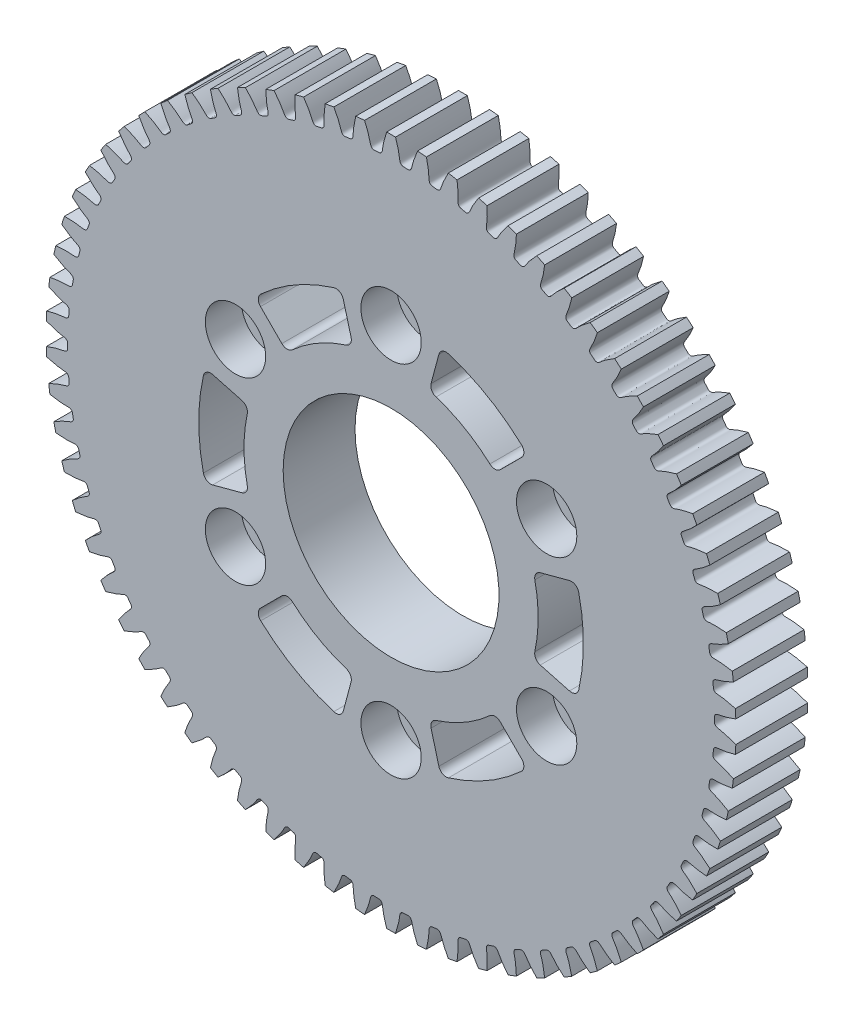
SolidWorks part; units mm, degrees
material "7075-T6 (SN)"
ref_plane "Front Plane" through (0, 0, 0) normal (0, 0, 1) x (1, 0, 0)
ref_plane "Top Plane" through (0, 0, 0) normal (0, 1, 0) x (1, 0, 0)
ref_plane "Right Plane" through (0, 0, 0) normal (1, 0, 0) x (0, 0, -1)
ref_axis "Axis4" through (0, 0, 0) along (0, 0, 1)
sketch "Sketch1" plane through (0, 0, 0) normal (0, 0, 1) x (1, 0, 0)
  arc A0 (45.2238, -6.7177) -> (45.3812, -5.5556) centre (0, 0) ccw
  arc A1 (45.6439, -2.6368) -> (45.6965, -1.4653) centre (0, 0) ccw
  arc A2 (45.6965, 1.4653) -> (45.6439, 2.6368) centre (0, 0) ccw
  arc A3 (45.3812, 5.5556) -> (45.2238, 6.7177) centre (0, 0) ccw
  arc A4 (44.7005, 9.6011) -> (44.4396, 10.7445) centre (0, 0) ccw
  arc A5 (43.6599, 13.5694) -> (43.2975, 14.6848) centre (0, 0) ccw
  arc A6 (42.2678, 17.4284) -> (41.8069, 18.5068) centre (0, 0) ccw
  arc A7 (40.5354, 21.1471) -> (39.9797, 22.1799) centre (0, 0) ccw
  arc A8 (38.4766, 24.6956) -> (37.8305, 25.6743) centre (0, 0) ccw
  arc A9 (36.108, 28.0452) -> (35.3768, 28.9621) centre (0, 0) ccw
  arc A10 (33.4487, 31.169) -> (32.6382, 32.0166) centre (0, 0) ccw
  arc A11 (30.5201, 34.0418) -> (29.6369, 34.8134) centre (0, 0) ccw
  arc A12 (27.3457, 36.6406) -> (26.3969, 37.3299) centre (0, 0) ccw
  arc A13 (23.9512, 38.9443) -> (22.9445, 39.5458) centre (0, 0) ccw
  arc A14 (20.3638, 40.9345) -> (19.3072, 41.4433) centre (0, 0) ccw
  arc A15 (16.6125, 42.5951) -> (15.5145, 43.0072) centre (0, 0) ccw
  arc A16 (12.7274, 43.9128) -> (11.597, 44.2248) centre (0, 0) ccw
  arc A17 (8.7399, 44.8769) -> (7.586, 45.0863) centre (0, 0) ccw
  arc A18 (4.682, 45.4796) -> (3.514, 45.5848) centre (0, 0) ccw
  arc A19 (0.5864, 45.7162) -> (-0.5864, 45.7162) centre (0, 0) ccw
  arc A20 (-3.514, 45.5848) -> (-4.682, 45.4796) centre (0, 0) ccw
  arc A21 (-7.586, 45.0863) -> (-8.7399, 44.8769) centre (0, 0) ccw
  arc A22 (-11.597, 44.2248) -> (-12.7274, 43.9128) centre (0, 0) ccw
  arc A23 (-15.5145, 43.0072) -> (-16.6125, 42.5951) centre (0, 0) ccw
  arc A24 (-19.3072, 41.4433) -> (-20.3638, 40.9345) centre (0, 0) ccw
  arc A25 (-22.9445, 39.5458) -> (-23.9512, 38.9443) centre (0, 0) ccw
  arc A26 (-26.3969, 37.3299) -> (-27.3457, 36.6406) centre (0, 0) ccw
  arc A27 (-29.6369, 34.8134) -> (-30.5201, 34.0418) centre (0, 0) ccw
  arc A28 (-32.6382, 32.0166) -> (-33.4487, 31.169) centre (0, 0) ccw
  arc A29 (-35.3768, 28.9621) -> (-36.108, 28.0452) centre (0, 0) ccw
  arc A30 (-37.8305, 25.6743) -> (-38.4766, 24.6956) centre (0, 0) ccw
  arc A31 (-39.9797, 22.1799) -> (-40.5354, 21.1471) centre (0, 0) ccw
  arc A32 (-41.8069, 18.5068) -> (-42.2678, 17.4284) centre (0, 0) ccw
  arc A33 (-43.2975, 14.6848) -> (-43.6599, 13.5694) centre (0, 0) ccw
  arc A34 (-44.4396, 10.7445) -> (-44.7005, 9.6011) centre (0, 0) ccw
  arc A35 (-45.2238, 6.7177) -> (-45.3812, 5.5556) centre (0, 0) ccw
  arc A36 (-45.6439, 2.6368) -> (-45.6965, 1.4653) centre (0, 0) ccw
  arc A37 (-45.6965, -1.4653) -> (-45.6439, -2.6368) centre (0, 0) ccw
  arc A38 (-45.3812, -5.5556) -> (-45.2238, -6.7177) centre (0, 0) ccw
  arc A39 (-44.7005, -9.6011) -> (-44.4396, -10.7445) centre (0, 0) ccw
  arc A40 (-43.6599, -13.5694) -> (-43.2975, -14.6848) centre (0, 0) ccw
  arc A41 (-42.2678, -17.4284) -> (-41.8069, -18.5068) centre (0, 0) ccw
  arc A42 (-40.5354, -21.1471) -> (-39.9797, -22.1799) centre (0, 0) ccw
  arc A43 (-38.4766, -24.6956) -> (-37.8305, -25.6743) centre (0, 0) ccw
  arc A44 (-36.108, -28.0452) -> (-35.3768, -28.9621) centre (0, 0) ccw
  arc A45 (-33.4487, -31.169) -> (-32.6382, -32.0166) centre (0, 0) ccw
  arc A46 (-30.5201, -34.0418) -> (-29.6369, -34.8134) centre (0, 0) ccw
  arc A47 (-27.3457, -36.6406) -> (-26.3969, -37.3299) centre (0, 0) ccw
  arc A48 (-23.9512, -38.9443) -> (-22.9445, -39.5458) centre (0, 0) ccw
  arc A49 (-20.3638, -40.9345) -> (-19.3072, -41.4433) centre (0, 0) ccw
  arc A50 (-16.6125, -42.5951) -> (-15.5145, -43.0072) centre (0, 0) ccw
  arc A51 (-12.7274, -43.9128) -> (-11.597, -44.2248) centre (0, 0) ccw
  arc A52 (-8.7399, -44.8769) -> (-7.586, -45.0863) centre (0, 0) ccw
  arc A53 (-4.682, -45.4796) -> (-3.514, -45.5848) centre (0, 0) ccw
  arc A54 (-0.5864, -45.7162) -> (0.5864, -45.7162) centre (0, 0) ccw
  arc A55 (3.514, -45.5848) -> (4.682, -45.4796) centre (0, 0) ccw
  arc A56 (7.586, -45.0863) -> (8.7399, -44.8769) centre (0, 0) ccw
  arc A57 (11.597, -44.2248) -> (12.7274, -43.9128) centre (0, 0) ccw
  arc A58 (15.5145, -43.0072) -> (16.6125, -42.5951) centre (0, 0) ccw
  arc A59 (19.3072, -41.4433) -> (20.3638, -40.9345) centre (0, 0) ccw
  arc A60 (22.9445, -39.5458) -> (23.9512, -38.9443) centre (0, 0) ccw
  arc A61 (26.3969, -37.3299) -> (27.3457, -36.6406) centre (0, 0) ccw
  arc A62 (29.6369, -34.8134) -> (30.5201, -34.0418) centre (0, 0) ccw
  arc A63 (32.6382, -32.0166) -> (33.4487, -31.169) centre (0, 0) ccw
  arc A64 (35.3768, -28.9621) -> (36.108, -28.0452) centre (0, 0) ccw
  arc A65 (37.8305, -25.6743) -> (38.4766, -24.6956) centre (0, 0) ccw
  arc A66 (39.9797, -22.1799) -> (40.5354, -21.1471) centre (0, 0) ccw
  arc A67 (41.8069, -18.5068) -> (42.2678, -17.4284) centre (0, 0) ccw
  arc A68 (43.2975, -14.6848) -> (43.6599, -13.5694) centre (0, 0) ccw
  arc A69 (44.4396, -10.7445) -> (44.7005, -9.6011) centre (0, 0) ccw
  spline S0 degree 3 number of poles 75 (44.7005, -9.6011) -> (45.2238, -6.7177)
  spline S1 degree 3 number of poles 75 (45.3812, -5.5556) -> (45.6439, -2.6368)
  spline S2 degree 3 number of poles 75 (45.6965, -1.4653) -> (45.6965, 1.4653)
  spline S3 degree 3 number of poles 75 (45.6439, 2.6368) -> (45.3812, 5.5556)
  spline S4 degree 3 number of poles 75 (45.2238, 6.7177) -> (44.7005, 9.6011)
  spline S5 degree 3 number of poles 75 (44.4396, 10.7445) -> (43.6599, 13.5694)
  spline S6 degree 3 number of poles 75 (43.2975, 14.6848) -> (42.2678, 17.4284)
  spline S7 degree 3 number of poles 75 (41.8069, 18.5068) -> (40.5354, 21.1471)
  spline S8 degree 3 number of poles 75 (39.9797, 22.1799) -> (38.4766, 24.6956)
  spline S9 degree 3 number of poles 75 (37.8305, 25.6743) -> (36.108, 28.0452)
  spline S10 degree 3 number of poles 75 (35.3768, 28.9621) -> (33.4487, 31.169)
  spline S11 degree 3 number of poles 75 (32.6382, 32.0166) -> (30.5201, 34.0418)
  spline S12 degree 3 number of poles 75 (29.6369, 34.8134) -> (27.3457, 36.6406)
  spline S13 degree 3 number of poles 75 (26.3969, 37.3299) -> (23.9512, 38.9443)
  spline S14 degree 3 number of poles 75 (22.9445, 39.5458) -> (20.3638, 40.9345)
  spline S15 degree 3 number of poles 75 (19.3072, 41.4433) -> (16.6125, 42.5951)
  spline S16 degree 3 number of poles 75 (15.5145, 43.0072) -> (12.7274, 43.9128)
  spline S17 degree 3 number of poles 75 (11.597, 44.2248) -> (8.7399, 44.8769)
  spline S18 degree 3 number of poles 75 (7.586, 45.0863) -> (4.682, 45.4796)
  spline S19 degree 3 number of poles 75 (3.514, 45.5848) -> (0.5864, 45.7162)
  spline S20 degree 3 number of poles 75 (-0.5864, 45.7162) -> (-3.514, 45.5848)
  spline S21 degree 3 number of poles 75 (-4.682, 45.4796) -> (-7.586, 45.0863)
  spline S22 degree 3 number of poles 75 (-8.7399, 44.8769) -> (-11.597, 44.2248)
  spline S23 degree 3 number of poles 75 (-12.7274, 43.9128) -> (-15.5145, 43.0072)
  spline S24 degree 3 number of poles 75 (-16.6125, 42.5951) -> (-19.3072, 41.4433)
  spline S25 degree 3 number of poles 75 (-20.3638, 40.9345) -> (-22.9445, 39.5458)
  spline S26 degree 3 number of poles 75 (-23.9512, 38.9443) -> (-26.3969, 37.3299)
  spline S27 degree 3 number of poles 75 (-27.3457, 36.6406) -> (-29.6369, 34.8134)
  spline S28 degree 3 number of poles 75 (-30.5201, 34.0418) -> (-32.6382, 32.0166)
  spline S29 degree 3 number of poles 75 (-33.4487, 31.169) -> (-35.3768, 28.9621)
  spline S30 degree 3 number of poles 75 (-36.108, 28.0452) -> (-37.8305, 25.6743)
  spline S31 degree 3 number of poles 75 (-38.4766, 24.6956) -> (-39.9797, 22.1799)
  spline S32 degree 3 number of poles 75 (-40.5354, 21.1471) -> (-41.8069, 18.5068)
  spline S33 degree 3 number of poles 75 (-42.2678, 17.4284) -> (-43.2975, 14.6848)
  spline S34 degree 3 number of poles 75 (-43.6599, 13.5694) -> (-44.4396, 10.7445)
  spline S35 degree 3 number of poles 75 (-44.7005, 9.6011) -> (-45.2238, 6.7177)
  spline S36 degree 3 number of poles 75 (-45.3812, 5.5556) -> (-45.6439, 2.6368)
  spline S37 degree 3 number of poles 75 (-45.6965, 1.4653) -> (-45.6965, -1.4653)
  spline S38 degree 3 number of poles 75 (-45.6439, -2.6368) -> (-45.3812, -5.5556)
  spline S39 degree 3 number of poles 75 (-45.2238, -6.7177) -> (-44.7005, -9.6011)
  spline S40 degree 3 number of poles 75 (-44.4396, -10.7445) -> (-43.6599, -13.5694)
  spline S41 degree 3 number of poles 75 (-43.2975, -14.6848) -> (-42.2678, -17.4284)
  spline S42 degree 3 number of poles 75 (-41.8069, -18.5068) -> (-40.5354, -21.1471)
  spline S43 degree 3 number of poles 75 (-39.9797, -22.1799) -> (-38.4766, -24.6956)
  spline S44 degree 3 number of poles 75 (-37.8305, -25.6743) -> (-36.108, -28.0452)
  spline S45 degree 3 number of poles 75 (-35.3768, -28.9621) -> (-33.4487, -31.169)
  spline S46 degree 3 number of poles 75 (-32.6382, -32.0166) -> (-30.5201, -34.0418)
  spline S47 degree 3 number of poles 75 (-29.6369, -34.8134) -> (-27.3457, -36.6406)
  spline S48 degree 3 number of poles 75 (-26.3969, -37.3299) -> (-23.9512, -38.9443)
  spline S49 degree 3 number of poles 75 (-22.9445, -39.5458) -> (-20.3638, -40.9345)
  spline S50 degree 3 number of poles 75 (-19.3072, -41.4433) -> (-16.6125, -42.5951)
  spline S51 degree 3 number of poles 75 (-15.5145, -43.0072) -> (-12.7274, -43.9128)
  spline S52 degree 3 number of poles 75 (-11.597, -44.2248) -> (-8.7399, -44.8769)
  spline S53 degree 3 number of poles 75 (-7.586, -45.0863) -> (-4.682, -45.4796)
  spline S54 degree 3 number of poles 75 (-3.514, -45.5848) -> (-0.5864, -45.7162)
  spline S55 degree 3 number of poles 75 (0.5864, -45.7162) -> (3.514, -45.5848)
  spline S56 degree 3 number of poles 75 (4.682, -45.4796) -> (7.586, -45.0863)
  spline S57 degree 3 number of poles 75 (8.7399, -44.8769) -> (11.597, -44.2248)
  spline S58 degree 3 number of poles 75 (12.7274, -43.9128) -> (15.5145, -43.0072)
  spline S59 degree 3 number of poles 75 (16.6125, -42.5951) -> (19.3072, -41.4433)
  spline S60 degree 3 number of poles 75 (20.3638, -40.9345) -> (22.9445, -39.5458)
  spline S61 degree 3 number of poles 75 (23.9512, -38.9443) -> (26.3969, -37.3299)
  spline S62 degree 3 number of poles 75 (27.3457, -36.6406) -> (29.6369, -34.8134)
  spline S63 degree 3 number of poles 75 (30.5201, -34.0418) -> (32.6382, -32.0166)
  spline S64 degree 3 number of poles 75 (33.4487, -31.169) -> (35.3768, -28.9621)
  spline S65 degree 3 number of poles 75 (36.108, -28.0452) -> (37.8305, -25.6743)
  spline S66 degree 3 number of poles 75 (38.4766, -24.6956) -> (39.9797, -22.1799)
  spline S67 degree 3 number of poles 75 (40.5354, -21.1471) -> (41.8069, -18.5068)
  spline S68 degree 3 number of poles 75 (42.2678, -17.4284) -> (43.2975, -14.6848)
  spline S69 degree 3 number of poles 75 (43.6599, -13.5694) -> (44.4396, -10.7445)
extrude "Boss-Extrude1" add sketch "Sketch1" against normal blind 9.525
sketch "Sketch2" plane through (0, 0, 0) normal (0, 0, 1) x (1, 0, 0)
  line L0 (6.3358, 23.6455) -> (5.2995, 19.7779)
  line L1 (14.4784, 14.4784) -> (17.3097, 17.3097)
  line L2 (0, 0) -> (5.2995, 19.7779) construction
  line L3 (0, 0) -> (14.4784, 14.4784) construction
  line L4 (0, 0) -> (0, 15.8526) construction
  arc A0 (5.2995, 19.7779) -> (5.9598, 18.5669) centre (6.2654, 19.5191) ccw
  arc A1 (5.9598, 18.5669) -> (13.0996, 14.4448) centre (0, 0) cw
  arc A2 (13.0996, 14.4448) -> (14.4784, 14.4784) centre (13.7713, 15.1855) ccw
  arc A3 (17.3097, 17.3097) -> (17.2802, 18.7522) centre (16.6026, 18.0168) ccw
  arc A4 (17.2802, 18.7522) -> (7.5997, 24.3412) centre (0, 0) ccw
  arc A5 (7.5997, 24.3412) -> (6.3358, 23.6455) centre (7.3017, 23.3866) ccw
  point P13 (0, 0)
  point P16 (0, 0)
  dimension "D3" = 19.5
  dimension "D4" = 25.5
  dimension "D5" = 1
  dimension "D1" = 15
  dimension "D2" = 30
extrude "Cut-Extrude1" cut sketch "Sketch2" against normal through all
sketch "Sketch3" plane through (0, 0, 0) normal (0, 0, 1) x (1, 0, 0)
  line L0 (0, 0) -> (0, 23.8125) construction
  circle A0 centre (0, 23.8125) radius 4
  dimension "D2" = 8
  dimension "D1" = 23.8125
extrude "Cut-Extrude2" cut sketch "Sketch3" against normal blind 4.7625
sketch "Sketch4" plane through (0, 0, -9.525) normal (0, 0, -1) x (-1, 0, 0)
  circle A0 centre (0, 23.8125) radius 2.15
  circle A1 centre (0, 23.8125) radius 4 construction
  point P2 (-1.4684, 24.873)
  dimension "D1" = 4.3
extrude "Cut-Extrude3" cut sketch "Sketch4" against normal through all
sketch "Sketch5" plane through (0, 0, -9.525) normal (0, 0, -1) x (-1, 0, 0)
  circle A0 centre (0, 0) radius 14.3065
  point P2 (0, 0)
  dimension "D1" = 28.6131
extrude "Cut-Extrude4" cut sketch "Sketch5" against normal through all
pattern_circular "CirPattern4" count 6 over 360 about axis through (0, 0, 0) along (0, 0, 1) of "Cut-Extrude1", "Cut-Extrude2", "Cut-Extrude3"
